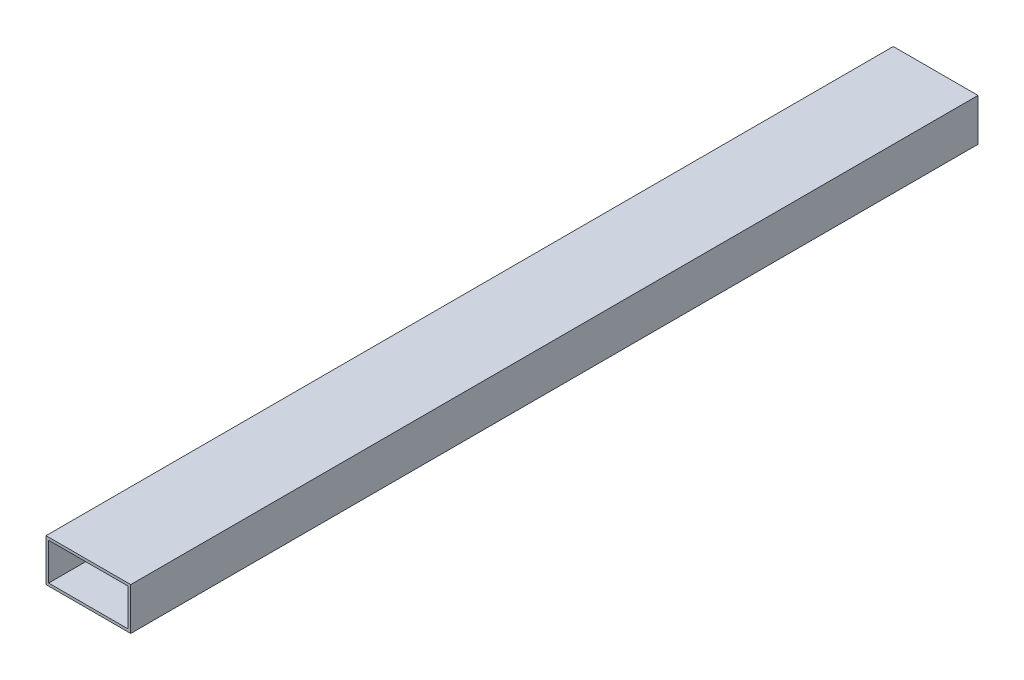
SolidWorks part; units mm, degrees
ref_plane "Front Plane" through (0, 0, 0) normal (0, 0, 1) x (1, 0, 0)
ref_plane "Top Plane" through (0, 0, 0) normal (0, 1, 0) x (1, 0, 0)
ref_plane "Right Plane" through (0, 0, 0) normal (1, 0, 0) x (0, 0, -1)
sketch "Sketch1" plane through (0, 0, 0) normal (0, 0, 1) x (1, 0, 0)
  line L0 (-23.8125, 11.1125) -> (23.8125, 11.1125)
  line L2 (-25.4, 12.7) -> (25.4, 12.7)
  line L3 (-25.4, 12.7) -> (-25.4, -12.7)
  line L4 (-25.4, -12.7) -> (25.4, -12.7)
  line L5 (25.4, 12.7) -> (25.4, -12.7)
  line L10 (23.8125, 11.1125) -> (23.8125, -11.1125)
  line L11 (-23.8125, -11.1125) -> (23.8125, -11.1125)
  line L12 (-23.8125, 11.1125) -> (-23.8125, -11.1125)
  point P12 (0, 12.7)
  point P14 (25.4, 0)
  dimension "Wall Thickness" = 1.5875
  dimension "Outside Width" = 50.8
  dimension "Outside Height" = 25.4
  dimension "Inside Height" = 22.225
  dimension "Inside Width" = 47.625
sketch "Sketch2" plane through (0, 0, 0) normal (1, 0, 0) x (0, 0, -1)
  line L0 (254, 0) -> (-254, 0)
  point P4 (0, 0)
  point P7 (-254, 0)
  point P10 (254, 0)
  dimension "Length" = 508
sketch "Sketch3" plane through (0, 0, 0) normal (0, 0, 1) x (1, 0, 0)
  line L21 (25.4, 12.7) -> (-25.4, 12.7)
  line L22 (25.4, -12.7) -> (25.4, 12.7)
  line L23 (-25.4, -12.7) -> (25.4, -12.7)
  line L24 (-25.4, 12.7) -> (-25.4, -12.7)
  line L25 (25.4, 12.7) -> (-25.4, 12.7)
  line L26 (25.4, -12.7) -> (25.4, 12.7)
  line L27 (-25.4, -12.7) -> (25.4, -12.7)
  line L28 (-25.4, 12.7) -> (-25.4, -12.7)
  line L29 (23.8125, 11.1125) -> (-23.8125, 11.1125)
  line L30 (23.8125, -11.1125) -> (23.8125, 11.1125)
  line L31 (-23.8125, -11.1125) -> (23.8125, -11.1125)
  line L32 (-23.8125, 11.1125) -> (-23.8125, -11.1125)
  line L33 (23.8125, 11.1125) -> (-23.8125, 11.1125)
  line L34 (23.8125, -11.1125) -> (23.8125, 11.1125)
  line L35 (-23.8125, -11.1125) -> (23.8125, -11.1125)
  line L36 (-23.8125, 11.1125) -> (-23.8125, -11.1125)
  dimension "D1" = 0
  dimension "D2" = 0
extrude "Boss-Extrude1" add sketch "Sketch3" along normal up to vertex (254 mm away) and the other way up to vertex (254 mm away) up to point (0, 0, 254) other way up to point (0, 0, -254)
sketch "Drawing Reference" plane through (0, 0, 0) normal (1, 0, 0) x (0, 0, -1)
  line L0 (-254, 0) -> (254, 0) construction
  line L1 (0, -12.7) -> (0, 12.7) construction
  line L2 (-254, -12.7) -> (254, -12.7) construction
  line L5 (-254, 12.7) -> (254, 12.7) construction
  point P7 (-217.424, 0)
  point P8 (217.424, 0)
  dimension "D1" = 36.576
equation "\"D1@Drawing Reference\"=\"Outside Width@Sketch1\" * 0.72"
